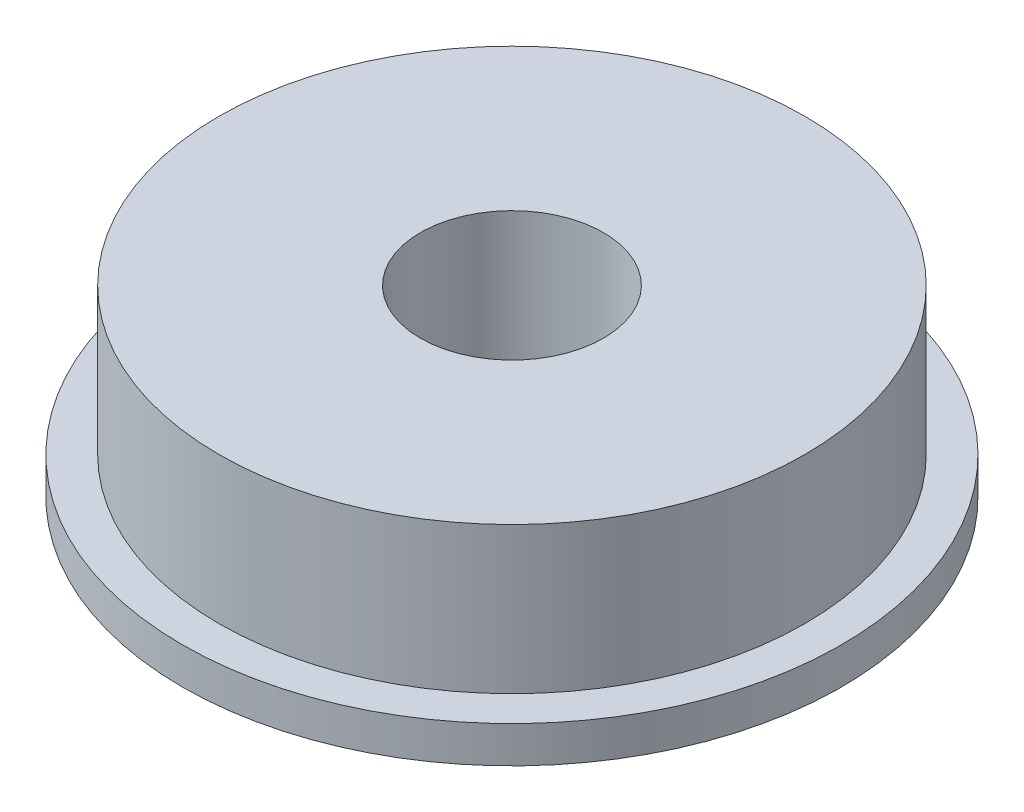
SolidWorks part; units mm, degrees
ref_plane "Alzado" through (0, 0, 0) normal (0, 0, 1) x (1, 0, 0)
ref_plane "Planta" through (0, 0, 0) normal (0, 1, 0) x (1, 0, 0)
ref_plane "Vista lateral" through (0, 0, 0) normal (1, 0, 0) x (0, 0, -1)
sketch "Croquis1" plane through (0, 0, 0) normal (0, 1, 0) x (1, 0, 0)
  circle A0 centre (0, 0) radius 2.5
  circle A1 centre (0, 0) radius 8
  circle A2 centre (0, 0) radius 9
  dimension "D1" = 5
  dimension "D2" = 16
  dimension "D3" = 18
extrude "Saliente-Extruir1" add sketch "Croquis1" along normal blind 1 contours A2 A1 region at (-8.7454, 0, 0)
extrude "Saliente-Extruir2" add sketch "Croquis1<3>" along normal blind 5 contours A1 A0 region at (-7.7737, 0, 0)
sketch "Croquis1<3>" plane through (0, 0, 0) normal (0, 1, 0) x (1, 0, 0) same geometry as "Croquis1"
